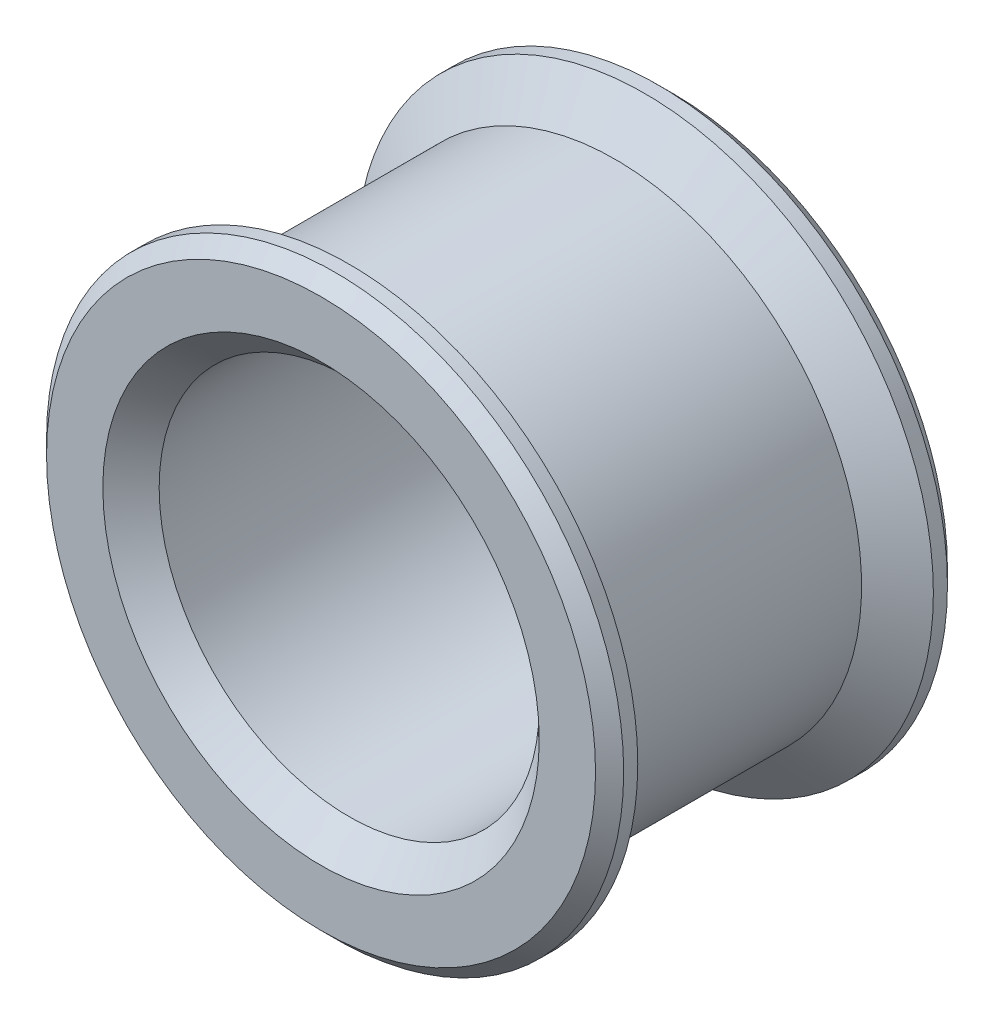
SolidWorks part; units mm, degrees
material "PLA"
ref_plane "Front Plane" through (0, 0, 0) normal (0, 0, 1) x (1, 0, 0)
ref_plane "Top Plane" through (0, 0, 0) normal (0, 1, 0) x (1, 0, 0)
ref_plane "Right Plane" through (0, 0, 0) normal (1, 0, 0) x (0, 0, -1)
sketch "Sketch1" plane through (0, 0, 0) normal (0, 0, 1) x (1, 0, 0)
  circle A0 centre (0, 0) radius 6.75
  circle A1 centre (0, 0) radius 8.75
  dimension "D1" = 13.5
  dimension "D2" = 2
extrude "Boss-Extrude1" add sketch "Sketch1" along normal mid plane 10.5
sketch "Sketch2" plane through (0, 0, 5.25) normal (0, 0, 1) x (1, 0, 0)
  circle A1 centre (0, 0) radius 6.75 construction
  circle A2 centre (0, 0) radius 10.25
  circle A3 centre (0, 0) radius 10.25
  circle A4 centre (0, 0) radius 6.75
  dimension "D1" = 1.5
extrude "Boss-Extrude2" add sketch "Sketch2" along normal blind 1
mirror "Mirror1" about plane through (0, 0, 0) normal (0, 0, 1) of "Boss-Extrude2"
chamfer "Chamfer1" distance 1.5 angle 35 2 edges at (8.75, 0, -5.25) (8.75, 0, 5.25) first distance on face at (8.75, 0, -5.25) first distance on face at (8.75, 0, 5.25)
chamfer "Chamfer2" distance 1 angle 45 2 edges at (6.75, 0, -6.25) (6.75, 0, 6.25)
chamfer "Chamfer3" distance 0.5 angle 45 2 edges at (10.25, 0, -6.25) (10.25, 0, 6.25)
